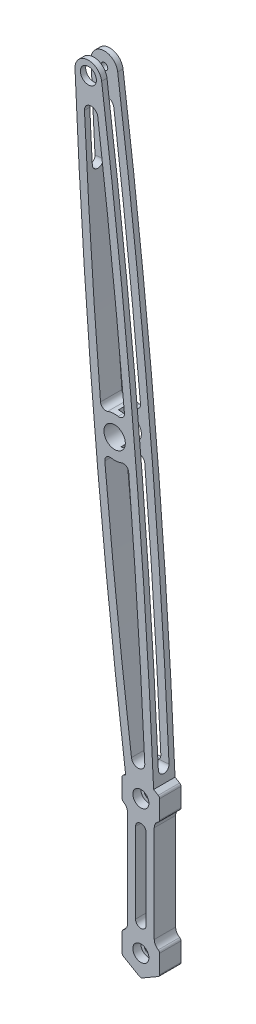
SolidWorks part; units mm, degrees
material "A2017"
ref_plane "正面" through (0, 0, 0) normal (0, 0, 1) x (1, 0, 0)
ref_plane "平面" through (0, 0, 0) normal (0, 1, 0) x (1, 0, 0)
ref_plane "右側面" through (0, 0, 0) normal (1, 0, 0) x (0, 0, -1)
sketch "ｽｹｯﾁ1" plane through (0, 0, 0) normal (0, 0, 1) x (1, 0, 0)
  line L0 (0, 0) -> (9.0749, 0) construction
  line L1 (0, 25) -> (0, 0) construction
  line L2 (0, -16.9171) -> (7, -20.9585)
  line L3 (7, 20.9585) -> (7, 29.0415)
  line L4 (7, 29.0415) -> (0, 33.0829)
  line L5 (0, 33.0829) -> (-7, 29.0415)
  line L6 (-7, 29.0415) -> (-7, 20.9585)
  line L7 (-7, 20.9585) -> (0, 16.9171)
  line L8 (0, 16.9171) -> (7, 20.9585)
  line L9 (-7, -20.9585) -> (0, -16.9171)
  line L10 (-7, -29.0415) -> (-7, -20.9585)
  line L11 (0, -33.0829) -> (-7, -29.0415)
  line L12 (7, -29.0415) -> (0, -33.0829)
  line L13 (7, -20.9585) -> (7, -29.0415)
  circle A0 centre (0, 25) radius 3
  circle A1 centre (0, -25) radius 3
  circle A2 centre (0, 25) radius 7 construction
  circle A3 centre (0, -25) radius 7 construction
  dimension "D1" = 6
  dimension "D2" = 50
  dimension "D3" = 14
extrude "ﾎﾞｽ - 押し出し1" add sketch "ｽｹｯﾁ1" along normal mid plane 8
sketch "ｽｹｯﾁ2" plane through (0, 0, 4) normal (0, 0, 1) x (1, 0, 0)
  line L0 (-7, 20.9585) -> (0, 16.9171) construction
  line L1 (5, -19.8038) -> (-5, -19.8038)
  line L2 (5, -19.8038) -> (5, 19.8038)
  line L3 (5, 19.8038) -> (-5, 19.8038)
  line L4 (-5, -19.8038) -> (-5, 19.8038)
  line L5 (5, -19.8038) -> (-5, 19.8038) construction
  line L6 (5, 19.8038) -> (-5, -19.8038) construction
  point P0 (0, 0)
  dimension "D1" = 10
extrude "ﾎﾞｽ - 押し出し2" add sketch "ｽｹｯﾁ2" against normal up to surface (8 mm away) up to face at (0, 25, -4)
fillet "ﾌｨﾚｯﾄ1" radius 3 4 edges at (5, -19.8038, 0) (-5, 19.8038, 0) (-5, -19.8038, 0) (5, 19.8038, 0)
fillet "ﾌｨﾚｯﾄ2" radius 1 10 edges at (-7, 20.9585, 0) (-7, 29.0415, 0) (0, 33.0829, 0) (7, 29.0415, 0) (7, 20.9585, 0) (7, -29.0415, 0) (0, -33.0829, 0) (-7, -29.0415, 0) (-7, -20.9585, 0) (7, -20.9585, 0)
sketch "ｽｹｯﾁ3" plane through (0, 0, -4) normal (0, 0, -1) x (-1, 0, 0)
  line L0 (0, -15) -> (0, 15) construction
  line L1 (-2, -15) -> (-2, 15)
  line L2 (2, -15) -> (2, 15)
  arc A0 (-2, -15) -> (2, -15) centre (0, -15) ccw
  arc A1 (2, 15) -> (-2, 15) centre (0, 15) ccw
  point P2 (0, 0)
  dimension "D1" = 4
  dimension "D2" = 30
extrude "ｶｯﾄ - 押し出し1" cut sketch "ｽｹｯﾁ3" against normal up to surface (8 mm away) up to face at (0, 0, 4)
sketch "ｽｹｯﾁ5" plane through (0, 0, 4) normal (0, 0, 1) x (1, 0, 0)
  circle A0 centre (0, -25) radius 3 construction
  circle A1 centre (0, 25) radius 3 construction
  circle A2 centre (0, -25) radius 3
  circle A3 centre (0, 25) radius 3
extrude "ﾎﾞｽ - 押し出し3" [suppressed] add sketch "ｽｹｯﾁ5" against normal blind 5
sketch "ｽｹｯﾁ8" plane through (0, 0, -4) normal (0, 0, -1) x (-1, 0, 0)
  circle A0 centre (0, -25) radius 3 construction
  circle A1 centre (0, 25) radius 3 construction
  circle A2 centre (0, -25) radius 3
  circle A3 centre (0, 25) radius 3
extrude "ﾎﾞｽ - 押し出し4" add sketch "ｽｹｯﾁ8" against normal blind 5
hole_wizard "M3 すきま穴1" positions "ｽｹｯﾁ6" profile "ｽｹｯﾁ7" hole size "M3" standard "JIS" end condition through all
sketch "ｽｹｯﾁ6" plane through (0, 0, 4) normal (0, 0, -1) x (-1, 0, 0)
  point P0 (0, 25)
  point P3 (0, -25)
sketch "ｽｹｯﾁ7" plane through (0, 25, 4) normal (1, 0, 0) x (0, -1, 0)
  line L0 (0, 0) -> (0, 8)
  line L1 (0, 8) -> (1.7, 8)
  line L2 (1.7, 8) -> (1.7, 0)
  line L5 (1.7, 0) -> (0, 0)
  line L11 (0, -6.35) -> (0, 107.95) construction
  dimension "通し穴の直径" = 3.4
  dimension "通し穴の深さ" = 8
sketch "ｽｹｯﾁ9" plane through (0, 0, 4) normal (0, 0, 1) x (1, 0, 0)
  line L0 (0, 25) -> (0, 298.9535) construction
  line L1 (0, 25) -> (-19.61, 249.1438) construction
  line L2 (0, 25) -> (-19.61, 249.1438) construction
  line L3 (-7.4715, 24.3463) -> (-27.0815, 248.4901) construction
  line L4 (7.4715, 25.6537) -> (-12.1386, 249.7975) construction
  line L15 (-7, 28.4641) -> (-7, 21.5359)
  line L16 (-5, 18.0718) -> (-5, -18.0718)
  line L17 (-7, -21.5359) -> (-7, -28.4641)
  line L18 (-6.5, -29.3301) -> (-0.5, -32.7942)
  line L19 (0.5, -32.7942) -> (6.5, -29.3301)
  line L20 (7, -28.4641) -> (7, -21.5359)
  line L21 (5, -18.0718) -> (5, 18.0718)
  line L22 (7, 21.5359) -> (7, 28.4641)
  line L23 (6.5, 29.3301) -> (0.5, 32.7942)
  line L24 (-0.5, 32.7942) -> (-6.5, 29.3301)
  line L25 (-7, 28.4641) -> (-7, 21.5359)
  line L26 (-5, 18.0718) -> (-5, -18.0718)
  line L27 (-7, -21.5359) -> (-7, -28.4641)
  line L28 (-6.5, -29.3301) -> (-0.5, -32.7942)
  line L29 (0.5, -32.7942) -> (6.5, -29.3301)
  line L30 (7, -28.4641) -> (7, -21.5359)
  line L31 (5, -18.0718) -> (5, 18.0718)
  line L32 (7, 21.5359) -> (7, 28.4641)
  line L33 (6.5, 29.3301) -> (0.5, 32.7942)
  line L34 (-0.5, 32.7942) -> (-6.5, 29.3301)
  arc A0 (-7.4715, 24.3463) -> (7.4715, 25.6537) centre (0, 25) ccw construction
  arc A1 (-12.1386, 249.7975) -> (-27.0815, 248.4901) centre (-19.61, 249.1438) ccw construction
  circle A2 centre (-19.61, 249.1438) radius 5 construction
  circle A3 centre (0, 25) radius 5
  arc A4 (-14.6533, 249.8004) -> (4.9954, 25.2141) centre (-2530.1776, -83.4321) cw
  arc A5 (-24.6055, 248.9297) -> (-4.9567, 24.3434) centre (2510.5676, 357.5759) ccw
  arc A6 (-14.6533, 249.8004) -> (-24.6055, 248.9297) centre (-19.61, 249.1438) ccw
  arc A16 (-7, 21.5359) -> (-6.5, 20.6699) centre (-6, 21.5359) ccw
  arc A17 (-5, 18.0718) -> (-6.5, 20.6699) centre (-8, 18.0718) ccw
  arc A18 (-6.5, -20.6699) -> (-5, -18.0718) centre (-8, -18.0718) ccw
  arc A19 (-6.5, -20.6699) -> (-7, -21.5359) centre (-6, -21.5359) ccw
  arc A20 (-7, -28.4641) -> (-6.5, -29.3301) centre (-6, -28.4641) ccw
  arc A21 (-0.5, -32.7942) -> (0.5, -32.7942) centre (0, -31.9282) ccw
  arc A22 (6.5, -29.3301) -> (7, -28.4641) centre (6, -28.4641) ccw
  arc A23 (7, -21.5359) -> (6.5, -20.6699) centre (6, -21.5359) ccw
  arc A24 (5, -18.0718) -> (6.5, -20.6699) centre (8, -18.0718) ccw
  arc A25 (6.5, 20.6699) -> (5, 18.0718) centre (8, 18.0718) ccw
  arc A26 (6.5, 20.6699) -> (7, 21.5359) centre (6, 21.5359) ccw
  arc A27 (7, 28.4641) -> (6.5, 29.3301) centre (6, 28.4641) ccw
  arc A28 (0.5, 32.7942) -> (-0.5, 32.7942) centre (0, 31.9282) ccw
  arc A29 (-6.5, 29.3301) -> (-7, 28.4641) centre (-6, 28.4641) ccw
  arc A30 (-7, 21.5359) -> (-6.5, 20.6699) centre (-6, 21.5359) ccw
  arc A31 (-5, 18.0718) -> (-6.5, 20.6699) centre (-8, 18.0718) ccw
  arc A32 (-6.5, -20.6699) -> (-5, -18.0718) centre (-8, -18.0718) ccw
  arc A33 (-6.5, -20.6699) -> (-7, -21.5359) centre (-6, -21.5359) ccw
  arc A34 (-7, -28.4641) -> (-6.5, -29.3301) centre (-6, -28.4641) ccw
  arc A35 (-0.5, -32.7942) -> (0.5, -32.7942) centre (0, -31.9282) ccw
  arc A36 (6.5, -29.3301) -> (7, -28.4641) centre (6, -28.4641) ccw
  arc A37 (7, -21.5359) -> (6.5, -20.6699) centre (6, -21.5359) ccw
  arc A38 (5, -18.0718) -> (6.5, -20.6699) centre (8, -18.0718) ccw
  arc A39 (6.5, 20.6699) -> (5, 18.0718) centre (8, 18.0718) ccw
  arc A40 (6.5, 20.6699) -> (7, 21.5359) centre (6, 21.5359) ccw
  arc A41 (7, 28.4641) -> (6.5, 29.3301) centre (6, 28.4641) ccw
  arc A42 (0.5, 32.7942) -> (-0.5, 32.7942) centre (0, 31.9282) ccw
  arc A43 (-6.5, 29.3301) -> (-7, 28.4641) centre (-6, 28.4641) ccw
  point P4 (-9.805, 137.0719)
  arc M28 (0.5, 32.7942) -> (-0.5, 32.7942) centre (0, 31.9282) ccw
  line M29 (-0.5, 32.7942) -> (-6.5, 29.3301)
  dimension "D5" = 10
  dimension "D1" = 5
  dimension "D2" = 225
  dimension "D4" = 15
  dimension "D3" = 0
extrude "ﾎﾞｽ - 押し出し5" add sketch "ｽｹｯﾁ9" against normal up to surface (8 mm away) contours A4 A6 A5 L33 M29 M28 region at (-10.1534, 141.0541, 4) up to face at (1.7, 25, -4)
sketch "ｽｹｯﾁ12" plane through (0, 0, -4) normal (0, 0, -1) x (-1, 0, 0)
  line L0 (19.61, 249.1438) -> (0, 25) construction
hole_wizard "M3 ねじ穴1" positions "ｽｹｯﾁ19" profile "ｽｹｯﾁ20" tap size "M3" standard "JIS" end condition through all
sketch "ｽｹｯﾁ19" plane through (0, 0, 4) normal (0, 0, 1) x (1, 0, 0)
  point P0 (-19.61, 249.1438)
sketch "ｽｹｯﾁ20" plane through (-19.61, 249.1438, 4) normal (1, 0, 0) x (0, -1, 0)
  line L0 (0, 0) -> (0, 8)
  line L1 (0, 8) -> (1.25, 8)
  line L2 (1.25, 8) -> (1.25, 0)
  line L5 (1.25, 0) -> (0, 0)
  line L11 (0, -6.35) -> (0, 107.95) construction
  dimension "次ｻｰﾌｪｽまでのねじ下穴ﾄﾞﾘﾙ直径" = 2.5
  dimension "次ｻｰﾌｪｽまでのねじ下穴ﾄﾞﾘﾙの深さ" = 8
cosmetic thread "穴のねじ山1" parameters "D2"=3
sketch "ｽｹｯﾁ10" plane through (0, 0, 4) normal (0, 0, 1) x (1, 0, 0)
  circle A0 centre (-19.61, 249.1438) radius 3
  dimension "D1" = 6
extrude "ｶｯﾄ - 押し出し2" cut sketch "ｽｹｯﾁ10" against normal blind 6
sketch "ｽｹｯﾁ21" plane through (0, 0, -4) normal (0, 0, -1) x (-1, 0, 0)
  circle A0 centre (19.61, 249.1438) radius 3
  dimension "D1" = 6
extrude "ｶｯﾄ - 押し出し8" [suppressed] cut sketch "ｽｹｯﾁ21" against normal blind 6
ref_plane "平面1" through (2.1706, 0.1899, 0) normal (0.9962, 0.0872, 0) x (0.0872, -0.9962, 0)
sketch "ｽｹｯﾁ13" plane through (0, 0, -4) normal (0, 0, -1) x (-1, 0, 0)
  line L0 (19.61, 249.1438) -> (0, 25) construction
  arc A2 (17.6274, 249.4065) -> (-1.7741, 30.1938) centre (2530.1776, -83.4321) ccw
  arc A3 (17.6274, 249.4065) -> (-1.7741, 30.1938) centre (2530.1776, -83.4321) ccw
  arc A4 (21.0716, 237.1884) -> (16.0946, 237.6238) centre (18.5745, 237.3071) ccw
  arc A5 (2.6995, 30.1943) -> (21.6082, 249.0582) centre (-2510.5676, 357.5759) ccw
  arc A6 (2.6995, 30.1943) -> (21.6082, 249.0582) centre (-2510.5676, 357.5759) ccw
  arc A7 (-1.4616, 36.9554) -> (3.5154, 36.52) centre (1.0356, 36.8367) ccw
  dimension "D3" = 5
  dimension "D1" = 3
  dimension "D2" = 3
extrude "ｶｯﾄ - 押し出し3" cut sketch "ｽｹｯﾁ13" against normal through all contours A3 A7 A6 A4 region at (-9.805, 137.0719, -4)
sketch "ｽｹｯﾁ14" plane through (0, 0, -4) normal (0, 0, -1) x (-1, 0, 0)
  line L0 (14.2879, 136.6797) -> (5.3221, 137.4641) construction
  arc A0 (3.5154, 36.52) -> (21.0716, 237.1884) centre (-2510.5676, 357.5759) ccw construction
  arc A1 (16.0946, 237.6238) -> (-1.4616, 36.9554) centre (2530.1776, -83.4321) ccw construction
  circle A2 centre (9.805, 137.0719) radius 7.5
  arc A3 (5.6744, 29.8068) -> (24.6055, 248.9297) centre (-2510.5676, 357.5759) ccw construction
extrude "ﾎﾞｽ - 押し出し6" add sketch "ｽｹｯﾁ14" against normal up to surface (8 mm away) up to face at (-9.805, 137.0719, 4)
fillet "ﾌｨﾚｯﾄ3" radius 2 4 edges at (-4.8058, 131.481, 0) (-13.7574, 130.6978, 0) (-14.8042, 142.6628, 0) (-5.8526, 143.446, 0)
sketch "ｽｹｯﾁ15" plane through (0, 0, 4) normal (0, 0, 1) x (1, 0, 0)
  line L0 (-19.61, 249.1438) -> (0, 25) construction
  circle A0 centre (-9.805, 137.0719) radius 4
  dimension "D1" = 8
extrude "ｶｯﾄ - 押し出し4" cut sketch "ｽｹｯﾁ15" against normal through all
sketch "ｽｹｯﾁ16" plane through (2.1706, 0.1899, 0) normal (0.9962, 0.0872, 0) x (0.0872, -0.9962, 0)
  line L0 (-254.9049, 0) -> (-34.9049, 0) construction
  line L1 (-254.9049, 4) -> (-254.9049, -4) construction
  line L2 (-254.9049, 2) -> (-34.9049, 2)
  line L3 (-254.9049, -2) -> (-34.9049, -2)
  arc A0 (-254.9049, 2) -> (-254.9049, -2) centre (-254.9049, 0) ccw
  arc A1 (-34.9049, -2) -> (-34.9049, 2) centre (-34.9049, 0) ccw
  point P5 (-144.9049, 0)
  dimension "D1" = 4
  dimension "D2" = 220
extrude "ｶｯﾄ - 押し出し6" cut sketch "ｽｹｯﾁ16" along normal through all
sketch "ｽｹｯﾁ22" plane through (2.1706, 0.1899, 0) normal (0.9962, 0.0872, 0) x (0, 0, -1)
  line L0 (0, 254.9049) -> (0, 219.9049) construction
  line L1 (-2, 254.9049) -> (2, 254.9049) construction
  line L2 (2, 254.9049) -> (2, 219.9049)
  line L3 (-2, 254.9049) -> (-2, 219.9049)
  line L4 (2, 252.9049) -> (2, 254.9049) construction
  arc A0 (2, 254.9049) -> (-2, 254.9049) centre (0, 254.9049) ccw
  arc A1 (-2, 219.9049) -> (2, 219.9049) centre (0, 219.9049) ccw
  point P5 (0, 237.4049)
  dimension "D1" = 35
extrude "ｶｯﾄ - 押し出し9" cut sketch "ｽｹｯﾁ22" against normal through all
